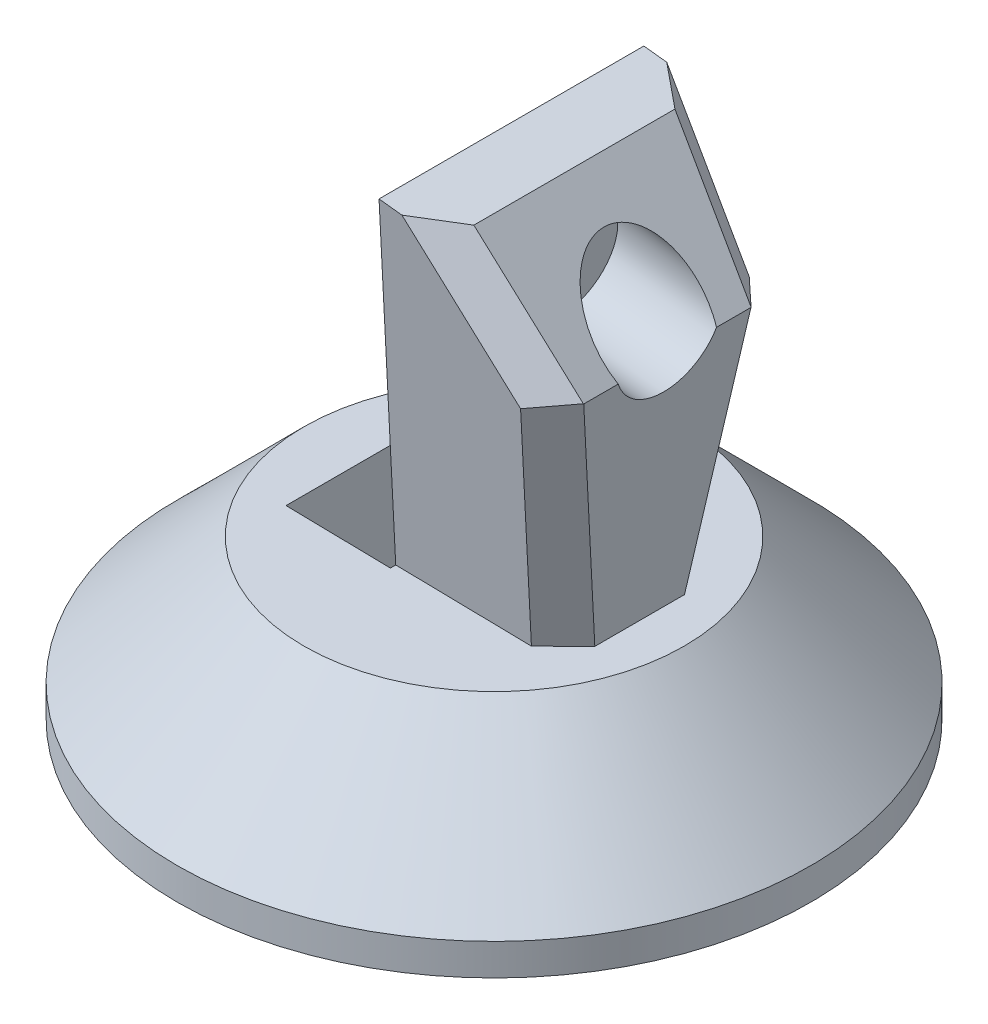
SolidWorks part; units mm, degrees
material "3D printed plastic"
ref_plane "Front Plane" through (0, 0, 0) normal (0, 0, 1) x (1, 0, 0)
ref_plane "Top Plane" through (0, 0, 0) normal (0, 1, 0) x (1, 0, 0)
ref_plane "Right Plane" through (0, 0, 0) normal (1, 0, 0) x (0, 0, -1)
sketch "Sketch1" plane through (0, 0, 0) normal (0, 0, 1) x (1, 0, 0)
  line L0 (-30, 0) -> (-30, 3)
  line L1 (-30, 3) -> (-18, 15)
  line L2 (-18, 15) -> (0, 15)
  line L3 (0, 15) -> (0, 0) construction
  line L4 (0, 0) -> (-30, 0)
  line L5 (0, 15) -> (0, 0)
  dimension "D1" = 60
  dimension "D2" = 3
  dimension "D3" = 15
  dimension "D4" = 45
revolve "Revolve1" add sketch "Sketch1" angle 360 about L3
ref_axis "Axis1" through (0, 0, -33) along (0, 0, 1)
ref_plane "Plane1" through (0, 0, 0) normal (0.9936, -0.1132, 0) x (0, 0, 1)
sketch "Sketch2" plane through (0, 0, 0) normal (0.9936, -0.1132, 0) x (0, 0, 1)
  line L0 (17.9187, -15.097) -> (-17.9187, -15.097) construction
  line L1 (7.8665, -16.9412) -> (5.5, -2)
  line L2 (5.5, -2) -> (-5.5, -2)
  line L3 (-5.5, -2) -> (-7.8665, -16.9412)
  line L4 (-7.8665, -16.9412) -> (7.8665, -16.9412)
  line L5 (0, -16.9412) -> (0, -2) construction
  line L6 (0, -2) -> (0, 0) construction
  ellipse E4 centre (0, -14.9036) end of major axis (-18, -14.9036) minor radius 2.0377 construction
  dimension "D1" = 2
  dimension "D2" = 18
  dimension "D3" = 11
extrude "Cut-Extrude1" cut sketch "Sketch2" against normal blind 10 from offset 4 offset against normal yes
sketch "Sketch3" plane through (-3.9743, 0.4528, 0) normal (-0.9936, 0.1132, 0) x (0, 0, 1)
  line L0 (-6.996, 14.6413) -> (-12.5394, 49.6413)
  line L1 (7.5022, 14.6413) -> (-7.5022, 14.6413) construction
  line L2 (-12.5394, 49.6413) -> (12.5394, 49.6413)
  line L3 (12.5394, 49.6413) -> (6.996, 14.6413)
  line L4 (6.996, 14.6413) -> (-6.996, 14.6413)
  line L5 (7.5022, 14.6413) -> (5.5, 2) construction
  line L6 (-5.5, 2) -> (-7.5022, 14.6413) construction
  line L7 (0, 14.6413) -> (0, 2) construction
  line L8 (5.5, 2) -> (-5.5, 2) construction
  dimension "D1" = 0.5
  dimension "D2" = 35
extrude "Boss-Extrude1" add sketch "Sketch3" against normal blind 16
chamfer "Chamfer3" distance 10 angle 45 1 edges at (17.5424, 47.9638, 0)
chamfer "Chamfer1" distance 3 angle 45 4 edges at (15.0985, 26.514, -9.1201) (15.0985, 26.514, 9.1201) (12.0085, 43.5619, -11.7475) (12.0085, 43.5619, 11.7475) first distance on face at (15.0985, 26.514, 0) first distance on face at (12.0085, 43.5619, 0)
sketch "Sketch4" plane through (0, 0, 0) normal (0, -1, 0) x (1, 0, 0)
  line L0 (-16, 0) -> (16, 0) construction
  circle A0 centre (-16, 0) radius 1.75
  circle A1 centre (16, 0) radius 1.75
  dimension "D2" = 3.5
  dimension "D1" = 32
extrude "Cut-Extrude2" cut sketch "Sketch4" against normal blind 11
sketch "Sketch5" plane through (11.9229, -1.3584, 0) normal (0.9936, -0.1132, 0) x (0, 0, -1)
  line L0 (0, 41.4643) -> (0, 0) construction
  line L1 (-4.2473, 16.4643) -> (4.2473, 16.4643) construction
  circle A0 centre (0, 41.4643) radius 1.5
  dimension "D1" = 3
  dimension "D2" = 25
extrude "Cut-Extrude3" cut sketch "Sketch5" against normal through all
sketch "Sketch6" plane through (11.9229, -1.3584, 0) normal (0.9936, -0.1132, 0) x (0, 0, -1)
  circle A0 centre (0, 41.4643) radius 5
  dimension "D1" = 10
extrude "Cut-Extrude4" cut sketch "Sketch6" against normal blind 10
